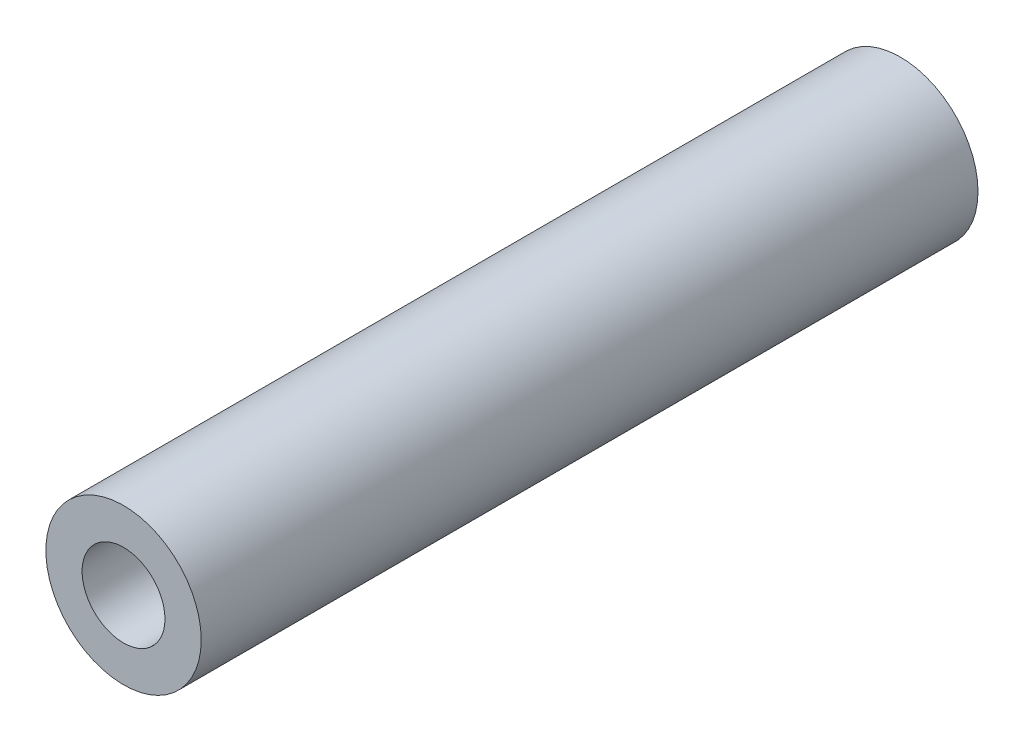
SolidWorks part; units mm, degrees
material "ABS"
ref_plane "Front Plane" through (0, 0, 0) normal (0, 0, 1) x (1, 0, 0)
ref_plane "Top Plane" through (0, 0, 0) normal (0, 1, 0) x (1, 0, 0)
ref_plane "Right Plane" through (0, 0, 0) normal (1, 0, 0) x (0, 0, -1)
sketch "Sketch1" plane through (0, 0, 0) normal (0, 0, 1) x (1, 0, 0)
  line L0 (0, 1.6) -> (0, 3) construction
  line L1 (0, -1.6) -> (0, -3) construction
  circle A0 centre (0, 0) radius 3
  circle A1 centre (0, 0) radius 1.6
  dimension "OD" = 6
  dimension "ID" = 3.2
sketch "Sketch2" plane through (0, 0, 0) normal (1, 0, 0) x (0, 0, -1)
  line L0 (-15, 1.6) -> (15, 1.6) construction
  line L1 (-15, -1.6) -> (15, -1.6) construction
  line L2 (-15, -3) -> (15, -3) construction
  line L3 (-15, 3) -> (15, 3) construction
  dimension "Length" = 30
extrude "Extrude1" add sketch "Sketch1" along normal up to vertex (15 mm away) and the other way up to vertex (15 mm away) up to point (0, 1.6, 15) other way up to point (0, 1.6, -15)
sketch "Sketch3" plane through (0, 0, 15) normal (0, 0, 1) x (1, 0, 0)
  circle A0 centre (0, 0) radius 1.6 construction
  circle A3 centre (0, 0) radius 1.6
  point P3 (-1.6, 0)
